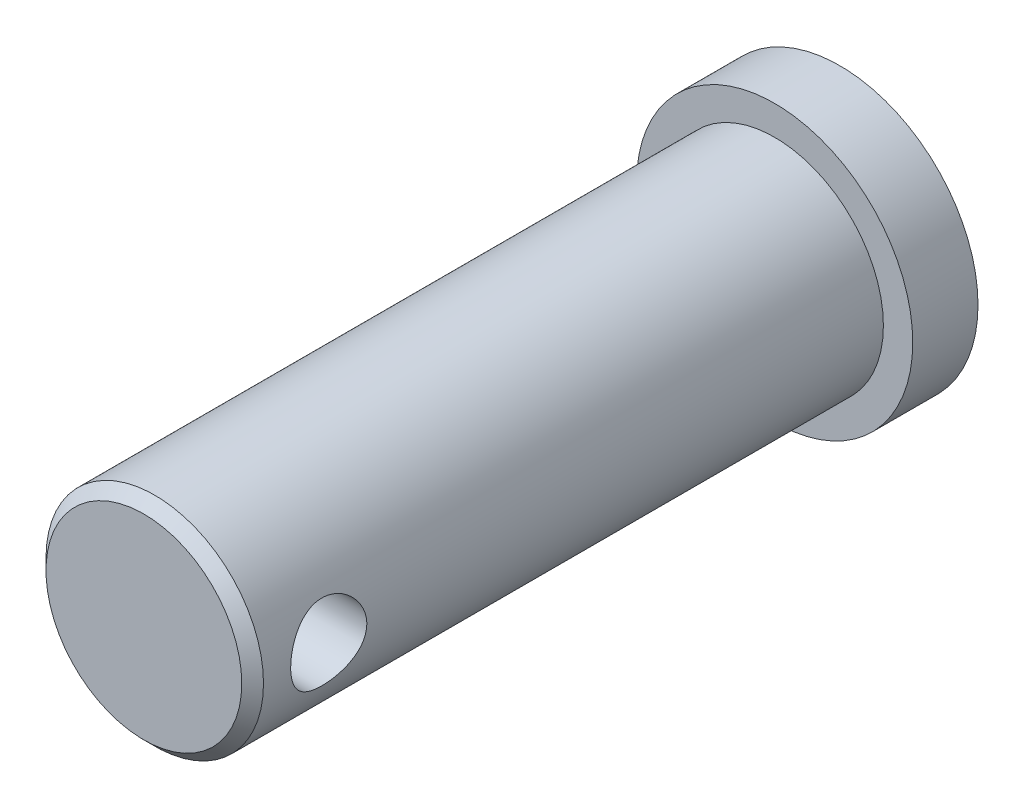
SolidWorks part; units mm, degrees
material "AISI 1020"
ref_plane "Plano frontal" through (0, 0, 0) normal (0, 0, 1) x (1, 0, 0)
ref_plane "Plano superior" through (0, 0, 0) normal (0, 1, 0) x (1, 0, 0)
ref_plane "Plano direito" through (0, 0, 0) normal (1, 0, 0) x (0, 0, -1)
sketch "Esboço1" plane through (0, 0, 0) normal (0, 0, 1) x (1, 0, 0)
  circle A0 centre (0, 0) radius 6.35
  circle A1 centre (0, 0) radius 5
  dimension "D1" = 10
  dimension "D2" = 12.7
extrude "Extrusão1" add sketch "Esboço1" along normal blind 29 contours A1 region at (0, 0, 0)
extrude "Extrusão2" add sketch "Esboço1<3>" against normal blind 3 contours A0
sketch "Esboço1<3>" plane through (0, 0, 0) normal (0, 0, 1) x (1, 0, 0) same geometry as "Esboço1"
sketch "Esboço2" plane through (0, 0, 0) normal (1, 0, 0) x (0, 0, -1)
  circle A0 centre (-25.5, 0) radius 1.75
  dimension "D1" = 3.5
  dimension "D2" = 25.5
extrude "Corte-extrusão1" cut sketch "Esboço2" against normal mid plane 15
chamfer "Chanfro1" distance 0.5 angle 45 1 edges at (5, 0, 29)
